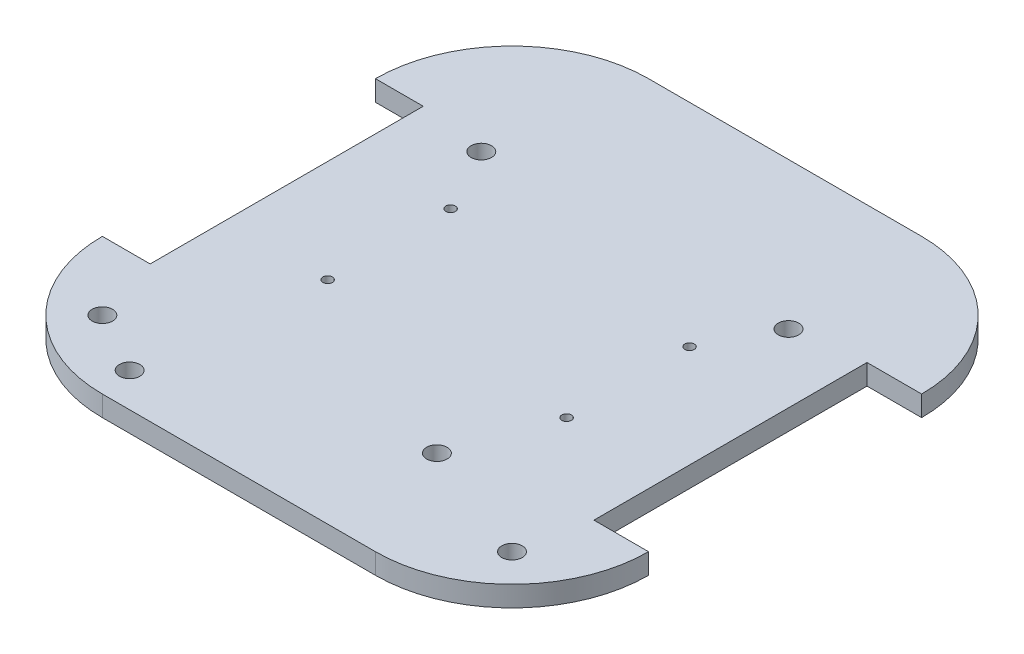
SolidWorks part; units mm, degrees
material "Pine"
ref_plane "Front Plane" through (0, 0, 0) normal (0, 0, 1) x (1, 0, 0)
ref_plane "Top Plane" through (0, 0, 0) normal (0, 1, 0) x (1, 0, 0)
ref_plane "Right Plane" through (0, 0, 0) normal (1, 0, 0) x (0, 0, -1)
sketch "Sketch3" plane through (0, 0, 0) normal (0, 1, 0) x (1, 0, 0)
  line L1 (0, 0) -> (80, 0)
  line L2 (0, 0) -> (0, 80)
  line L3 (0, 80) -> (80, 80)
  line L4 (80, 0) -> (80, 80)
  dimension "D1" = 80
  dimension "D2" = 80
extrude "Boss-Extrude1" add sketch "Sketch3" along normal blind 3
sketch "Sketch4" plane through (0, 3, 0) normal (0, 1, 0) x (1, 0, 0)
  line L0 (0, 80) -> (0, 0) construction
  line L1 (0, 60) -> (7, 60)
  line L2 (0, 60) -> (0, 20)
  line L3 (0, 20) -> (7, 20)
  line L4 (7, 60) -> (7, 20)
  line L5 (80, 80) -> (0, 80) construction
  line L6 (80, 0) -> (80, 80) construction
  line L7 (72, 60) -> (80, 60)
  line L8 (72, 60) -> (72, 20)
  line L9 (72, 20) -> (80, 20)
  line L10 (80, 60) -> (80, 20)
  dimension "D1" = 7
  dimension "D2" = 40
  dimension "D3" = 0
  dimension "D4" = 20
  dimension "D5" = 8
  dimension "D6" = 40
  dimension "D7" = 20
  dimension "D8" = 0
extrude "Cut-Extrude1" cut sketch "Sketch4" against normal blind 3
fillet "Fillet3" radius 20 1 edges at (0, 1.5, -80) type face fillet first side face at (0, 1.5, -70) second side face at (40, 1.5, -80)
fillet "Fillet4" radius 20 1 edges at (80, 1.5, -80) type face fillet first side face at (80, 1.5, -70) second side face at (50, 1.5, -80)
fillet "Fillet5" radius 20 1 edges at (80, 1.5, 0) type face fillet first side face at (80, 1.5, -10) second side face at (40, 1.5, 0)
fillet "Fillet6" radius 20 1 edges at (0, 1.5, 0) type face fillet first side face at (30, 1.5, 0) second side face at (0, 1.5, -10)
sketch "Sketch6" plane through (0, 3, 0) normal (0, 1, 0) x (1, 0, 0)
  line L0 (80, 60) -> (72, 60) construction
  line L1 (7, 20) -> (7, 60) construction
  line L2 (7, 60) -> (0, 60) construction
  line L3 (72, 60) -> (72, 20) construction
  circle A0 centre (17, 58.5) radius 1.5
  circle A1 centre (62, 58.5) radius 1.5
  dimension "D1" = 10
  dimension "D3" = 1.5
  dimension "D2" = 1.5
  dimension "D4" = 10
extrude "Cut-Extrude2" cut sketch "Sketch6" against normal blind 3
sketch "Sketch9" plane through (0, 3, 0) normal (0, 1, 0) x (1, 0, 0)
  line L0 (72, 20) -> (80, 20) construction
  line L1 (72, 60) -> (72, 20) construction
  line L2 (0, 20) -> (7, 20) construction
  line L3 (7, 20) -> (7, 60) construction
  circle A0 centre (70, 10) radius 1.5
  circle A1 centre (10, 10) radius 1.5
  dimension "D1" = 10
  dimension "D3" = 10
  dimension "D2" = 2
  dimension "D4" = 3
extrude "Cut-Extrude3" cut sketch "Sketch9" against normal blind 3
sketch "Sketch10" plane through (0, 3, 0) normal (0, 1, 0) x (1, 0, 0)
  line L0 (20, 0) -> (60, 0) construction
  line L1 (7, 20) -> (7, 60) construction
  circle A0 centre (19, 5) radius 1.5
  circle A1 centre (52, 17) radius 1.5
  dimension "D1" = 5
  dimension "D3" = 33
  dimension "D2" = 12
  dimension "D4" = 17
extrude "Cut-Extrude4" cut sketch "Sketch10" against normal blind 3
sketch "Sketch11" plane through (0, 3, 0) normal (0, 1, 0) x (1, 0, 0)
  line L1 (7, 20) -> (7, 60) construction
  line L2 (72, 60) -> (72, 20) construction
  circle A0 centre (22, 49) radius 0.7
  circle A1 centre (22, 31) radius 0.7
  circle A2 centre (57, 49) radius 0.7
  circle A3 centre (57, 31) radius 0.7
  dimension "D1" = 15
  dimension "D3" = 15
  dimension "D6" = 15
  dimension "D8" = 15
extrude "Cut-Extrude5" cut sketch "Sketch11" against normal blind 3
